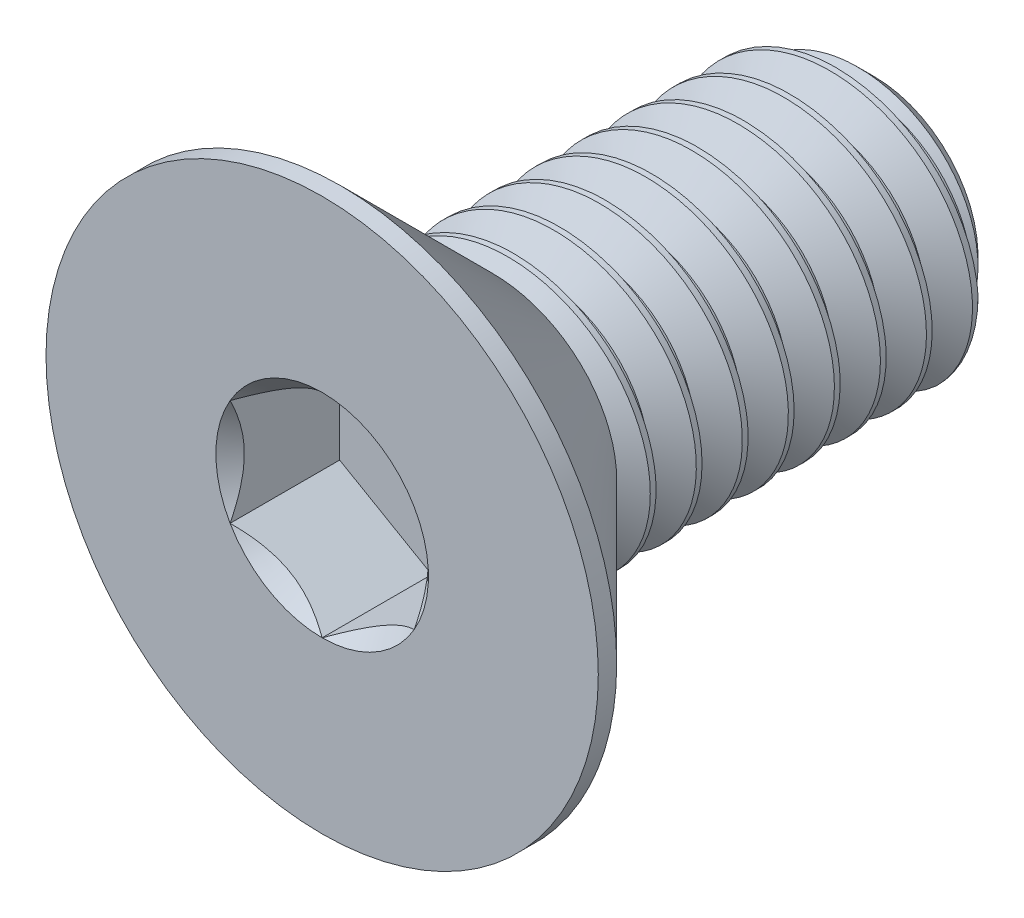
SolidWorks part; units mm, degrees
ref_plane "Front" through (0, 0, 0) normal (0, 0, 1) x (1, 0, 0)
ref_plane "Top" through (0, 0, 0) normal (0, 1, 0) x (1, 0, 0)
ref_plane "Right" through (0, 0, 0) normal (1, 0, 0) x (0, 0, -1)
sketch "Sketch1" plane through (0, 0, 0) normal (1, 0, 0) x (0, 0, -1)
  line L0 (0, 3) -> (0.2, 3) construction
  line L1 (0.2, 3) -> (1.7, 1.5) construction
  line L2 (0, 1.5) -> (6, 1.5)
  line L3 (6, 1.5) -> (6, 0)
  line L4 (6, 0) -> (0, 0)
  line L5 (0, 0) -> (0, 3) construction
  line L6 (0, 3) -> (0, -3) construction
  line L7 (6, 1.5) -> (6, -1.5) construction
  line L8 (0, -3) -> (0.2, -3) construction
  line L9 (0.2, -3) -> (1.7, -1.5) construction
  line L11 (0, 1.5) -> (0, 0)
  line L12 (1.7, 1.5) -> (1.7, 0) construction
  dimension "Head Ht" = 1.7
  dimension "Head Dia" = 6
  dimension "Dia" = 3
  dimension "Lg" = 6
  dimension "Head Angle" = 90
revolve "Revolve1" add sketch "Sketch1" angle 360 about L4
sketch "Sketch3" plane through (0, 0, -6) normal (0, 0, -1) x (-1, 0, 0)
  circle A0 centre (0, 0) radius 1.5
curve "Helix/Spiral1" pitch 0.5 height 6 radius 1.5 centre (0, 0, -6) axis (0, 0, 1) start towards (0, 1, 0)
sketch "Sketch2" plane through (0, 0, 0) normal (1, 0, 0) x (0, 0, -1)
  line L0 (6, 1.5) -> (6.4375, 1.5)
  line L1 (6.4375, 1.5) -> (6.25, 1.1752)
  line L2 (6.25, 1.1752) -> (6.1875, 1.1752)
  line L3 (6.1875, 1.1752) -> (6, 1.5)
  line L4 (6.0938, 1.3376) -> (6.3437, 1.3376) construction
  dimension "D1" = 60
  dimension "D2" = 0.0625
  dimension "D3" = 0.25
chamfer "Chamfer1" distance 0.375 angle 45 1 edges at (0, 1.5, -6)
sweep "Cut-Sweep1" cut profiles "Sketch2" path "Helix/Spiral1"
sketch "Sketch7" plane through (0, 0, 0) normal (1, 0, 0) x (0, 0, -1)
  line L0 (0, 3) -> (0.2, 3) construction
  line L1 (0.2, 3) -> (1.7, 1.5) construction
  line L2 (0, 3) -> (0.2, 3)
  line L3 (0.2, 3) -> (1.7, 1.5)
  line L4 (1.7, 1.5) -> (1.7, 0) construction
  line L5 (1.7, 1.5) -> (1.7, 0)
  line L7 (0, 0) -> (0, 3) construction
  line L8 (0, 0) -> (0, 3)
  line L9 (0, 0) -> (1.7, 0)
  line L10 (3.3, 0) -> (-3.3, 0) construction
revolve "Revolve2" add sketch "Sketch7" angle 360 about L9
ref_plane "Plane1" through (0, 0, -1.7) normal (0, 0, 1) x (1, 0, 0)
sketch "Sketch8" plane through (0, 0, -1.7) normal (0, 0, 1) x (1, 0, 0)
  circle A0 centre (0, 0) radius 1.5
extrude "Boss-Extrude1" add sketch "Sketch8" against normal through all draft 45
sketch "Sketch5" plane through (0, 0, 0) normal (0, 0, 1) x (1, 0, 0)
  line L1 (1, -0.5774) -> (1, 0.5774)
  line L2 (1, 0.5774) -> (0, 1.1547)
  line L3 (0, 1.1547) -> (-1, 0.5774)
  line L4 (-1, 0.5774) -> (-1, -0.5774)
  line L5 (-1, -0.5774) -> (0, -1.1547)
  line L6 (0, -1.1547) -> (1, -0.5774)
  circle A0 centre (0, 0) radius 1 construction
  dimension "Hex" = 2
extrude "Cut-Extrude2" cut sketch "Sketch5" against normal blind 1.19
sketch "Sketch6" plane through (0, 0, 0) normal (0, 0, 1) x (1, 0, 0)
  circle A0 centre (0, 0) radius 1.1547
extrude "Cut-Extrude3" cut sketch "Sketch6" against normal blind 1.19 draft 45
sketch "Sketch9" [suppressed] plane through (0, 0, -5.5) normal (0, 0, 1) x (1, 0, 0)
  circle A1 centre (0, 0) radius 5
  circle A2 centre (0, 0) radius 5
  point P0 (0, 5)
  dimension "D1" = 0
extrude "Boss-Extrude2" [suppressed] add sketch "Sketch9" against normal offset from surface (18.5 mm away) 26 up to face at (0, 1.125, -6)
fillet "Fillet1" [suppressed] radius 0.3
sketch "Sketch10" plane through (0, 0, 0) normal (1, 0, 0) x (0, 0, -1)
  line L0 (6, 1.5) -> (6, -1.5) construction
  point P0 (5.25, -1.5)
  dimension "D1" = 0.75
equation "\"D3@Helix/Spiral1\" = \"Lg@Sketch1\""
equation "\"D2@Sketch2\" = \"D4@Helix/Spiral1\" * .125"
equation "\"D3@Sketch2\" = \"D4@Helix/Spiral1\" * .5"
equation "\"D1@Chamfer1\" = \"D4@Helix/Spiral1\" * .75"
equation "\"D1@Cut-Extrude2\" = \"Head Ht@Sketch1\" * .7"
equation "\"D1@Sketch10\" = \"D4@Helix/Spiral1\" * 1.5"
equation "\"D1@Cut-Extrude3\" = \"D1@Cut-Extrude2\""
equation "\"D1@Fillet1\" = \"Dia@Sketch1\" * .1"
